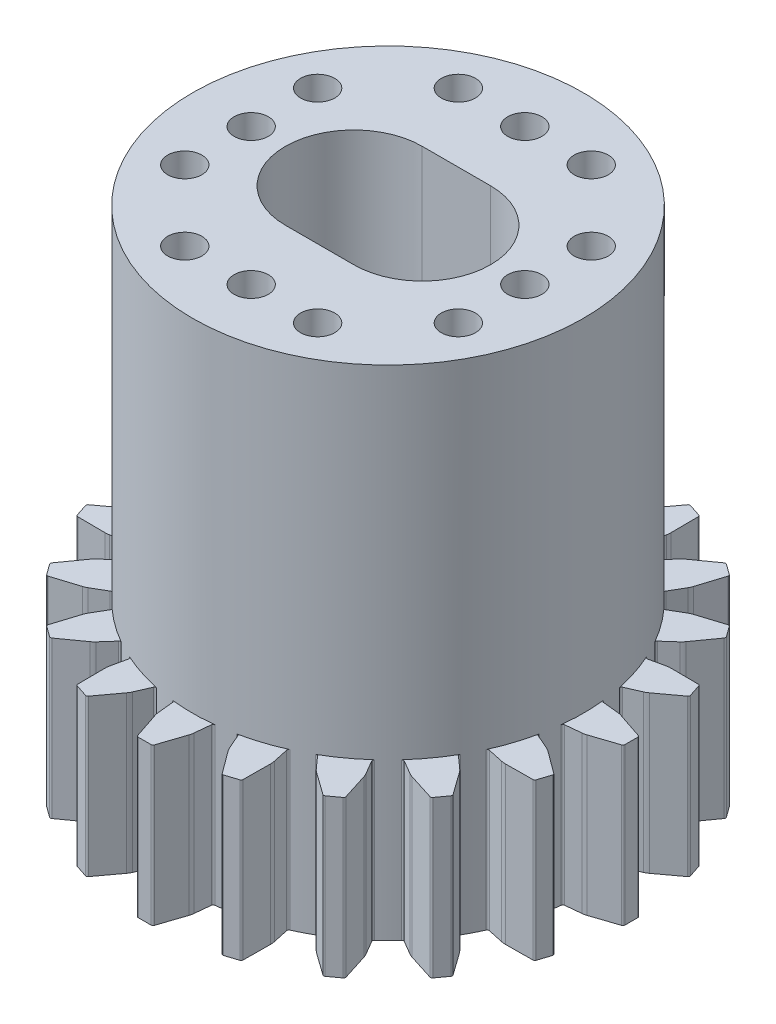
SolidWorks part; units mm, degrees
ref_plane "Front Plane" through (0, 0, 0) normal (0, 0, 1) x (1, 0, 0)
ref_plane "Top Plane" through (0, 0, 0) normal (0, 1, 0) x (1, 0, 0)
ref_plane "Right Plane" through (0, 0, 0) normal (1, 0, 0) x (0, 0, -1)
sketch "Sketch1" plane through (0, 0, 0) normal (0, 1, 0) x (1, 0, 0)
  line L0 (0, 23.8701) -> (0, -17.0658) construction
  line L1 (-0.9919, 10.0309) -> (-0.9111, 10.8389)
  line L2 (-0.8647, 11.0557) -> (-0.4228, 12.3815)
  line L3 (-0.3279, 12.4499) -> (0.3279, 12.4499)
  line L4 (0.4228, 12.3815) -> (0.8647, 11.0557)
  line L5 (0.9111, 10.8389) -> (0.9919, 10.0309)
  line L6 (2.1564, 9.8465) -> (2.4829, 10.59)
  line L7 (2.594, 10.7818) -> (3.424, 11.9062)
  line L8 (3.5353, 11.9419) -> (4.1591, 11.7392)
  line L9 (4.2282, 11.6449) -> (4.2388, 10.2473)
  line L10 (4.2159, 10.0269) -> (4.0431, 9.2334)
  line L11 (5.0936, 8.6982) -> (5.6339, 9.3044)
  line L12 (5.7988, 9.4525) -> (6.9356, 10.2654)
  line L13 (7.0526, 10.2649) -> (7.5831, 9.8794)
  line L14 (7.6197, 9.7683) -> (7.1979, 8.4359)
  line L15 (7.1081, 8.2333) -> (6.6985, 7.5322)
  line L16 (7.5322, 6.6985) -> (8.2333, 7.1081)
  line L17 (8.4359, 7.1979) -> (9.7683, 7.6197)
  line L18 (9.8794, 7.5831) -> (10.2649, 7.0526)
  line L19 (10.2654, 6.9356) -> (9.4525, 5.7988)
  line L20 (9.3044, 5.6339) -> (8.6982, 5.0936)
  line L21 (9.2334, 4.0431) -> (10.0269, 4.2159)
  line L22 (10.2473, 4.2388) -> (11.6449, 4.2282)
  line L23 (11.7392, 4.1591) -> (11.9419, 3.5353)
  line L24 (11.9062, 3.424) -> (10.7818, 2.594)
  line L25 (10.59, 2.4829) -> (9.8465, 2.1564)
  line L26 (10.0309, 0.9919) -> (10.8389, 0.9111)
  line L27 (11.0557, 0.8647) -> (12.3815, 0.4228)
  line L28 (12.4499, 0.3279) -> (12.4499, -0.3279)
  line L29 (12.3815, -0.4228) -> (11.0557, -0.8647)
  line L30 (10.8389, -0.9111) -> (10.0309, -0.9919)
  line L31 (9.8465, -2.1564) -> (10.59, -2.4829)
  line L32 (10.7818, -2.594) -> (11.9062, -3.424)
  line L33 (11.9419, -3.5353) -> (11.7392, -4.1591)
  line L34 (11.6449, -4.2282) -> (10.2473, -4.2388)
  line L35 (10.0269, -4.2159) -> (9.2334, -4.0431)
  line L36 (8.6982, -5.0936) -> (9.3044, -5.6339)
  line L37 (9.4525, -5.7988) -> (10.2654, -6.9356)
  line L38 (10.2649, -7.0526) -> (9.8794, -7.5831)
  line L39 (9.7683, -7.6197) -> (8.4359, -7.1979)
  line L40 (8.2333, -7.1081) -> (7.5322, -6.6985)
  line L41 (6.6985, -7.5322) -> (7.1081, -8.2333)
  line L42 (7.1979, -8.4359) -> (7.6197, -9.7683)
  line L43 (7.5831, -9.8794) -> (7.0526, -10.2649)
  line L44 (6.9356, -10.2654) -> (5.7988, -9.4525)
  line L45 (5.6339, -9.3044) -> (5.0936, -8.6982)
  line L46 (4.0431, -9.2334) -> (4.2159, -10.0269)
  line L47 (4.2388, -10.2473) -> (4.2282, -11.6449)
  line L48 (4.1591, -11.7392) -> (3.5353, -11.9419)
  line L49 (3.424, -11.9062) -> (2.594, -10.7818)
  line L50 (2.4829, -10.59) -> (2.1564, -9.8465)
  line L51 (0.9919, -10.0309) -> (0.9111, -10.8389)
  line L52 (0.8647, -11.0557) -> (0.4228, -12.3815)
  line L53 (0.3279, -12.4499) -> (-0.3279, -12.4499)
  line L54 (-0.4228, -12.3815) -> (-0.8647, -11.0557)
  line L55 (-0.9111, -10.8389) -> (-0.9919, -10.0309)
  line L56 (-2.1564, -9.8465) -> (-2.4829, -10.59)
  line L57 (-2.594, -10.7818) -> (-3.424, -11.9062)
  line L58 (-3.5353, -11.9419) -> (-4.1591, -11.7392)
  line L59 (-4.2282, -11.6449) -> (-4.2388, -10.2473)
  line L60 (-4.2159, -10.0269) -> (-4.0431, -9.2334)
  line L61 (-5.0936, -8.6982) -> (-5.6339, -9.3044)
  line L62 (-5.7988, -9.4525) -> (-6.9356, -10.2654)
  line L63 (-7.0526, -10.2649) -> (-7.5831, -9.8794)
  line L64 (-7.6197, -9.7683) -> (-7.1979, -8.4359)
  line L65 (-7.1081, -8.2333) -> (-6.6985, -7.5322)
  line L66 (-7.5322, -6.6985) -> (-8.2333, -7.1081)
  line L67 (-8.4359, -7.1979) -> (-9.7683, -7.6197)
  line L68 (-9.8794, -7.5831) -> (-10.2649, -7.0526)
  line L69 (-10.2654, -6.9356) -> (-9.4525, -5.7988)
  line L70 (-9.3044, -5.6339) -> (-8.6982, -5.0936)
  line L71 (-9.2334, -4.0431) -> (-10.0269, -4.2159)
  line L72 (-10.2473, -4.2388) -> (-11.6449, -4.2282)
  line L73 (-11.7392, -4.1591) -> (-11.9419, -3.5353)
  line L74 (-11.9062, -3.424) -> (-10.7818, -2.594)
  line L75 (-10.59, -2.4829) -> (-9.8465, -2.1564)
  line L76 (-10.0309, -0.9919) -> (-10.8389, -0.9111)
  line L77 (-11.0557, -0.8647) -> (-12.3815, -0.4228)
  line L78 (-12.4499, -0.3279) -> (-12.4499, 0.3279)
  line L79 (-12.3815, 0.4228) -> (-11.0557, 0.8647)
  line L80 (-10.8389, 0.9111) -> (-10.0309, 0.9919)
  line L81 (-9.8465, 2.1564) -> (-10.59, 2.4829)
  line L82 (-10.7818, 2.594) -> (-11.9062, 3.424)
  line L83 (-11.9419, 3.5353) -> (-11.7392, 4.1591)
  line L84 (-11.6449, 4.2282) -> (-10.2473, 4.2388)
  line L85 (-10.0269, 4.2159) -> (-9.2334, 4.0431)
  line L86 (-8.6982, 5.0936) -> (-9.3044, 5.6339)
  line L87 (-9.4525, 5.7988) -> (-10.2654, 6.9356)
  line L88 (-10.2649, 7.0526) -> (-9.8794, 7.5831)
  line L89 (-9.7683, 7.6197) -> (-8.4359, 7.1979)
  line L90 (-8.2333, 7.1081) -> (-7.5322, 6.6985)
  line L91 (-6.6985, 7.5322) -> (-7.1081, 8.2333)
  line L92 (-7.1979, 8.4359) -> (-7.6197, 9.7683)
  line L93 (-7.5831, 9.8794) -> (-7.0526, 10.2649)
  line L94 (-6.9356, 10.2654) -> (-5.7988, 9.4525)
  line L95 (-5.6339, 9.3044) -> (-5.0936, 8.6982)
  line L96 (-4.0431, 9.2334) -> (-4.2159, 10.0269)
  line L97 (-4.2388, 10.2473) -> (-4.2282, 11.6449)
  line L98 (-4.1591, 11.7392) -> (-3.5353, 11.9419)
  line L99 (-3.424, 11.9062) -> (-2.594, 10.7818)
  line L100 (-2.4829, 10.59) -> (-2.1564, 9.8465)
  arc A0 (-1.0806, 9.9414) -> (-2.0444, 9.7888) centre (0, 0) ccw
  arc A1 (0.8647, 11.0557) -> (0.9111, 10.8389) centre (-0.0839, 10.7394) cw
  arc A2 (-0.9111, 10.8389) -> (-0.8647, 11.0557) centre (0.0839, 10.7394) cw
  arc A3 (0.3279, 12.4499) -> (0.4228, 12.3815) centre (0.3279, 12.3499) cw
  arc A4 (-0.4228, 12.3815) -> (-0.3279, 12.4499) centre (-0.3279, 12.3499) cw
  arc A5 (0.9919, 10.0309) -> (1.0806, 9.9414) centre (1.0914, 10.0409) ccw
  arc A6 (-0.9919, 10.0309) -> (-1.0806, 9.9414) centre (-1.0914, 10.0409) cw
  arc A7 (2.1564, 9.8465) -> (2.0444, 9.7888) centre (2.0648, 9.8867) cw
  arc A8 (2.4829, 10.59) -> (2.594, 10.7818) centre (3.3985, 10.1879) cw
  arc A9 (3.424, 11.9062) -> (3.5353, 11.9419) centre (3.5044, 11.8468) cw
  arc A10 (4.1591, 11.7392) -> (4.2282, 11.6449) centre (4.1282, 11.6441) cw
  arc A11 (4.2388, 10.2473) -> (4.2159, 10.0269) centre (3.2388, 10.2397) cw
  arc A12 (4.0431, 9.2334) -> (4.0998, 9.121) centre (4.1408, 9.2122) ccw
  arc A13 (5.0936, 8.6982) -> (4.9692, 8.678) centre (5.0189, 8.7647) cw
  arc A14 (5.6339, 9.3044) -> (5.7988, 9.4525) centre (6.3804, 8.639) cw
  arc A15 (6.9356, 10.2654) -> (7.0526, 10.2649) centre (6.9938, 10.184) cw
  arc A16 (7.5831, 9.8794) -> (7.6197, 9.7683) centre (7.5244, 9.7985) cw
  arc A17 (7.1979, 8.4359) -> (7.1081, 8.2333) centre (6.2446, 8.7377) cw
  arc A18 (6.6985, 7.5322) -> (6.7177, 7.4076) centre (6.7848, 7.4817) ccw
  arc A19 (7.5322, 6.6985) -> (7.4076, 6.7177) centre (7.4817, 6.7848) cw
  arc A20 (8.2333, 7.1081) -> (8.4359, 7.1979) centre (8.7377, 6.2446) cw
  arc A21 (9.7683, 7.6197) -> (9.8794, 7.5831) centre (9.7985, 7.5244) cw
  arc A22 (10.2649, 7.0526) -> (10.2654, 6.9356) centre (10.184, 6.9938) cw
  arc A23 (9.4525, 5.7988) -> (9.3044, 5.6339) centre (8.639, 6.3804) cw
  arc A24 (8.6982, 5.0936) -> (8.678, 4.9692) centre (8.7647, 5.0189) ccw
  arc A25 (9.2334, 4.0431) -> (9.121, 4.0998) centre (9.2122, 4.1408) cw
  arc A26 (10.0269, 4.2159) -> (10.2473, 4.2388) centre (10.2397, 3.2388) cw
  arc A27 (11.6449, 4.2282) -> (11.7392, 4.1591) centre (11.6441, 4.1282) cw
  arc A28 (11.9419, 3.5353) -> (11.9062, 3.424) centre (11.8468, 3.5044) cw
  arc A29 (10.7818, 2.594) -> (10.59, 2.4829) centre (10.1879, 3.3985) cw
  arc A30 (9.8465, 2.1564) -> (9.7888, 2.0444) centre (9.8867, 2.0648) ccw
  arc A31 (10.0309, 0.9919) -> (9.9414, 1.0806) centre (10.0409, 1.0914) cw
  arc A32 (10.8389, 0.9111) -> (11.0557, 0.8647) centre (10.7394, -0.0839) cw
  arc A33 (12.3815, 0.4228) -> (12.4499, 0.3279) centre (12.3499, 0.3279) cw
  arc A34 (12.4499, -0.3279) -> (12.3815, -0.4228) centre (12.3499, -0.3279) cw
  arc A35 (11.0557, -0.8647) -> (10.8389, -0.9111) centre (10.7394, 0.0839) cw
  arc A36 (10.0309, -0.9919) -> (9.9414, -1.0806) centre (10.0409, -1.0914) ccw
  arc A37 (9.8465, -2.1564) -> (9.7888, -2.0444) centre (9.8867, -2.0648) cw
  arc A38 (10.59, -2.4829) -> (10.7818, -2.594) centre (10.1879, -3.3985) cw
  arc A39 (11.9062, -3.424) -> (11.9419, -3.5353) centre (11.8468, -3.5044) cw
  arc A40 (11.7392, -4.1591) -> (11.6449, -4.2282) centre (11.6441, -4.1282) cw
  arc A41 (10.2473, -4.2388) -> (10.0269, -4.2159) centre (10.2397, -3.2388) cw
  arc A42 (9.2334, -4.0431) -> (9.121, -4.0998) centre (9.2122, -4.1408) ccw
  arc A43 (8.6982, -5.0936) -> (8.678, -4.9692) centre (8.7647, -5.0189) cw
  arc A44 (9.3044, -5.6339) -> (9.4525, -5.7988) centre (8.639, -6.3804) cw
  arc A45 (10.2654, -6.9356) -> (10.2649, -7.0526) centre (10.184, -6.9938) cw
  arc A46 (9.8794, -7.5831) -> (9.7683, -7.6197) centre (9.7985, -7.5244) cw
  arc A47 (8.4359, -7.1979) -> (8.2333, -7.1081) centre (8.7377, -6.2446) cw
  arc A48 (7.5322, -6.6985) -> (7.4076, -6.7177) centre (7.4817, -6.7848) ccw
  arc A49 (6.6985, -7.5322) -> (6.7177, -7.4076) centre (6.7848, -7.4817) cw
  arc A50 (7.1081, -8.2333) -> (7.1979, -8.4359) centre (6.2446, -8.7377) cw
  arc A51 (7.6197, -9.7683) -> (7.5831, -9.8794) centre (7.5244, -9.7985) cw
  arc A52 (7.0526, -10.2649) -> (6.9356, -10.2654) centre (6.9938, -10.184) cw
  arc A53 (5.7988, -9.4525) -> (5.6339, -9.3044) centre (6.3804, -8.639) cw
  arc A54 (5.0936, -8.6982) -> (4.9692, -8.678) centre (5.0189, -8.7647) ccw
  arc A55 (4.0431, -9.2334) -> (4.0998, -9.121) centre (4.1408, -9.2122) cw
  arc A56 (4.2159, -10.0269) -> (4.2388, -10.2473) centre (3.2388, -10.2397) cw
  arc A57 (4.2282, -11.6449) -> (4.1591, -11.7392) centre (4.1282, -11.6441) cw
  arc A58 (3.5353, -11.9419) -> (3.424, -11.9062) centre (3.5044, -11.8468) cw
  arc A59 (2.594, -10.7818) -> (2.4829, -10.59) centre (3.3985, -10.1879) cw
  arc A60 (2.1564, -9.8465) -> (2.0444, -9.7888) centre (2.0648, -9.8867) ccw
  arc A61 (0.9919, -10.0309) -> (1.0806, -9.9414) centre (1.0914, -10.0409) cw
  arc A62 (0.9111, -10.8389) -> (0.8647, -11.0557) centre (-0.0839, -10.7394) cw
  arc A63 (0.4228, -12.3815) -> (0.3279, -12.4499) centre (0.3279, -12.3499) cw
  arc A64 (-0.3279, -12.4499) -> (-0.4228, -12.3815) centre (-0.3279, -12.3499) cw
  arc A65 (-0.8647, -11.0557) -> (-0.9111, -10.8389) centre (0.0839, -10.7394) cw
  arc A66 (-0.9919, -10.0309) -> (-1.0806, -9.9414) centre (-1.0914, -10.0409) ccw
  arc A67 (-2.1564, -9.8465) -> (-2.0444, -9.7888) centre (-2.0648, -9.8867) cw
  arc A68 (-2.4829, -10.59) -> (-2.594, -10.7818) centre (-3.3985, -10.1879) cw
  arc A69 (-3.424, -11.9062) -> (-3.5353, -11.9419) centre (-3.5044, -11.8468) cw
  arc A70 (-4.1591, -11.7392) -> (-4.2282, -11.6449) centre (-4.1282, -11.6441) cw
  arc A71 (-4.2388, -10.2473) -> (-4.2159, -10.0269) centre (-3.2388, -10.2397) cw
  arc A72 (-4.0431, -9.2334) -> (-4.0998, -9.121) centre (-4.1408, -9.2122) ccw
  arc A73 (-5.0936, -8.6982) -> (-4.9692, -8.678) centre (-5.0189, -8.7647) cw
  arc A74 (-5.6339, -9.3044) -> (-5.7988, -9.4525) centre (-6.3804, -8.639) cw
  arc A75 (-6.9356, -10.2654) -> (-7.0526, -10.2649) centre (-6.9938, -10.184) cw
  arc A76 (-7.5831, -9.8794) -> (-7.6197, -9.7683) centre (-7.5244, -9.7985) cw
  arc A77 (-7.1979, -8.4359) -> (-7.1081, -8.2333) centre (-6.2446, -8.7377) cw
  arc A78 (-6.6985, -7.5322) -> (-6.7177, -7.4076) centre (-6.7848, -7.4817) ccw
  arc A79 (-7.5322, -6.6985) -> (-7.4076, -6.7177) centre (-7.4817, -6.7848) cw
  arc A80 (-8.2333, -7.1081) -> (-8.4359, -7.1979) centre (-8.7377, -6.2446) cw
  arc A81 (-9.7683, -7.6197) -> (-9.8794, -7.5831) centre (-9.7985, -7.5244) cw
  arc A82 (-10.2649, -7.0526) -> (-10.2654, -6.9356) centre (-10.184, -6.9938) cw
  arc A83 (-9.4525, -5.7988) -> (-9.3044, -5.6339) centre (-8.639, -6.3804) cw
  arc A84 (-8.6982, -5.0936) -> (-8.678, -4.9692) centre (-8.7647, -5.0189) ccw
  arc A85 (-9.2334, -4.0431) -> (-9.121, -4.0998) centre (-9.2122, -4.1408) cw
  arc A86 (-10.0269, -4.2159) -> (-10.2473, -4.2388) centre (-10.2397, -3.2388) cw
  arc A87 (-11.6449, -4.2282) -> (-11.7392, -4.1591) centre (-11.6441, -4.1282) cw
  arc A88 (-11.9419, -3.5353) -> (-11.9062, -3.424) centre (-11.8468, -3.5044) cw
  arc A89 (-10.7818, -2.594) -> (-10.59, -2.4829) centre (-10.1879, -3.3985) cw
  arc A90 (-9.8465, -2.1564) -> (-9.7888, -2.0444) centre (-9.8867, -2.0648) ccw
  arc A91 (-10.0309, -0.9919) -> (-9.9414, -1.0806) centre (-10.0409, -1.0914) cw
  arc A92 (-10.8389, -0.9111) -> (-11.0557, -0.8647) centre (-10.7394, 0.0839) cw
  arc A93 (-12.3815, -0.4228) -> (-12.4499, -0.3279) centre (-12.3499, -0.3279) cw
  arc A94 (-12.4499, 0.3279) -> (-12.3815, 0.4228) centre (-12.3499, 0.3279) cw
  arc A95 (-11.0557, 0.8647) -> (-10.8389, 0.9111) centre (-10.7394, -0.0839) cw
  arc A96 (-10.0309, 0.9919) -> (-9.9414, 1.0806) centre (-10.0409, 1.0914) ccw
  arc A97 (-9.8465, 2.1564) -> (-9.7888, 2.0444) centre (-9.8867, 2.0648) cw
  arc A98 (-10.59, 2.4829) -> (-10.7818, 2.594) centre (-10.1879, 3.3985) cw
  arc A99 (-11.9062, 3.424) -> (-11.9419, 3.5353) centre (-11.8468, 3.5044) cw
  arc A100 (-11.7392, 4.1591) -> (-11.6449, 4.2282) centre (-11.6441, 4.1282) cw
  arc A101 (-10.2473, 4.2388) -> (-10.0269, 4.2159) centre (-10.2397, 3.2388) cw
  arc A102 (-9.2334, 4.0431) -> (-9.121, 4.0998) centre (-9.2122, 4.1408) ccw
  arc A103 (-8.6982, 5.0936) -> (-8.678, 4.9692) centre (-8.7647, 5.0189) cw
  arc A104 (-9.3044, 5.6339) -> (-9.4525, 5.7988) centre (-8.639, 6.3804) cw
  arc A105 (-10.2654, 6.9356) -> (-10.2649, 7.0526) centre (-10.184, 6.9938) cw
  arc A106 (-9.8794, 7.5831) -> (-9.7683, 7.6197) centre (-9.7985, 7.5244) cw
  arc A107 (-8.4359, 7.1979) -> (-8.2333, 7.1081) centre (-8.7377, 6.2446) cw
  arc A108 (-7.5322, 6.6985) -> (-7.4076, 6.7177) centre (-7.4817, 6.7848) ccw
  arc A109 (-6.6985, 7.5322) -> (-6.7177, 7.4076) centre (-6.7848, 7.4817) cw
  arc A110 (-7.1081, 8.2333) -> (-7.1979, 8.4359) centre (-6.2446, 8.7377) cw
  arc A111 (-7.6197, 9.7683) -> (-7.5831, 9.8794) centre (-7.5244, 9.7985) cw
  arc A112 (-7.0526, 10.2649) -> (-6.9356, 10.2654) centre (-6.9938, 10.184) cw
  arc A113 (-5.7988, 9.4525) -> (-5.6339, 9.3044) centre (-6.3804, 8.639) cw
  arc A114 (-5.0936, 8.6982) -> (-4.9692, 8.678) centre (-5.0189, 8.7647) ccw
  arc A115 (-4.0431, 9.2334) -> (-4.0998, 9.121) centre (-4.1408, 9.2122) cw
  arc A116 (-4.2159, 10.0269) -> (-4.2388, 10.2473) centre (-3.2388, 10.2397) cw
  arc A117 (-4.2282, 11.6449) -> (-4.1591, 11.7392) centre (-4.1282, 11.6441) cw
  arc A118 (-3.5353, 11.9419) -> (-3.424, 11.9062) centre (-3.5044, 11.8468) cw
  arc A119 (-2.594, 10.7818) -> (-2.4829, 10.59) centre (-3.3985, 10.1879) cw
  arc A120 (-2.1564, 9.8465) -> (-2.0444, 9.7888) centre (-2.0648, 9.8867) ccw
  arc A121 (-4.0998, 9.121) -> (-4.9692, 8.678) centre (0, 0) ccw
  arc A122 (-6.7177, 7.4076) -> (-7.4076, 6.7177) centre (0, 0) ccw
  arc A123 (-8.678, 4.9692) -> (-9.121, 4.0998) centre (0, 0) ccw
  arc A124 (-9.7888, 2.0444) -> (-9.9414, 1.0806) centre (0, 0) ccw
  arc A125 (-9.121, -4.0998) -> (-8.678, -4.9692) centre (0, 0) ccw
  arc A126 (-7.4076, -6.7177) -> (-6.7177, -7.4076) centre (0, 0) ccw
  arc A127 (-4.9692, -8.678) -> (-4.0998, -9.121) centre (0, 0) ccw
  arc A128 (-2.0444, -9.7888) -> (-1.0806, -9.9414) centre (0, 0) ccw
  arc A129 (1.0806, -9.9414) -> (2.0444, -9.7888) centre (0, 0) ccw
  arc A130 (4.0998, -9.121) -> (4.9692, -8.678) centre (0, 0) ccw
  arc A131 (6.7177, -7.4076) -> (7.4076, -6.7177) centre (0, 0) ccw
  arc A132 (8.678, -4.9692) -> (9.121, -4.0998) centre (0, 0) ccw
  arc A133 (9.7888, -2.0444) -> (9.9414, -1.0806) centre (0, 0) ccw
  arc A134 (9.9414, 1.0806) -> (9.7888, 2.0444) centre (0, 0) ccw
  arc A135 (9.121, 4.0998) -> (8.678, 4.9692) centre (0, 0) ccw
  arc A136 (7.4076, 6.7177) -> (6.7177, 7.4076) centre (0, 0) ccw
  arc A137 (4.9692, 8.678) -> (4.0998, 9.121) centre (0, 0) ccw
  arc A138 (2.0444, 9.7888) -> (1.0806, 9.9414) centre (0, 0) ccw
  arc A139 (-9.9414, -1.0806) -> (-9.7888, -2.0444) centre (0, 0) ccw
  point P7 (0, 12.4499)
  point P12 (0, 10)
  point P21 (0.9, 10.9499)
  point P24 (-0.9, 10.9499)
  point P27 (0.4, 12.4499)
  point P30 (-0.4, 12.4499)
  point P32 (1, 9.9499)
  point P35 (-1, 9.9499)
  point P374 (0, 0)
  dimension "D1" = 20
  dimension "D9" = 1
  dimension "D10" = 0.1
  dimension "D11" = 0.1
  dimension "D2" = 0.8
  dimension "D3" = 1
  dimension "D4" = 2.5
  dimension "D5" = 1
  dimension "D6" = 2
  dimension "D7" = 0.1
  dimension "D8" = 0.1
  dimension "D12" = 20
extrude "Boss-Extrude1" add sketch "Sketch1" along normal blind 8
sketch "Sketch2" plane through (0, 0, 0) normal (0, -1, 0) x (1, 0, 0)
  circle A0 centre (0, 0) radius 8
  circle A1 centre (0, 0) radius 5.5
  dimension "D1" = 16
  dimension "D2" = 11
extrude "Cut-Extrude1" cut sketch "Sketch2" against normal blind 2.9
sketch "Sketch3" plane through (0, 8, 0) normal (0, 1, 0) x (1, 0, 0)
  circle A0 centre (0, 0) radius 10
  dimension "D1" = 20
extrude "Boss-Extrude2" add sketch "Sketch3" along normal blind 17.5
sketch "Sketch4" plane through (0, 25.5, 0) normal (0, 1, 0) x (1, 0, 0)
  circle A0 centre (0, 7) radius 0.875
  circle A1 centre (3.4, 7) radius 0.875
  circle A2 centre (-3.4, 7) radius 0.875
  circle A3 centre (7, 3.4) radius 0.875
  circle A4 centre (7, 0) radius 0.875
  circle A5 centre (7, -3.4) radius 0.875
  circle A6 centre (3.4, -7) radius 0.875
  circle A7 centre (0, -7) radius 0.875
  circle A8 centre (-3.4, -7) radius 0.875
  circle A9 centre (-7, -3.4) radius 0.875
  circle A10 centre (-7, 0) radius 0.875
  circle A11 centre (-7, 3.4) radius 0.875
  point P27 (0, 0)
  dimension "D5" = 1.75
  dimension "D1" = 7
  dimension "D2" = 7
  dimension "D3" = 4
  dimension "D6" = 3.4
  dimension "D7" = 3.4
extrude "Cut-Extrude2" cut sketch "Sketch4" against normal blind 15
sketch "Sketch5" plane through (0, 0, 0) normal (0, -1, 0) x (1, 0, 0)
  line L0 (-1.75, 3.5) -> (1.75, 3.5)
  line L1 (-1.75, -3.5) -> (1.75, -3.5)
  line L2 (-1.75, 0) -> (1.75, 0) construction
  arc A0 (-1.75, 3.5) -> (-1.75, -3.5) centre (-1.75, 0) ccw
  arc A1 (1.75, -3.5) -> (1.75, 3.5) centre (1.75, 0) ccw
  point P6 (0, 0)
  dimension "D2" = 3.5
  dimension "D1" = 3.5
extrude "Cut-Extrude5" cut sketch "Sketch5" along direction (0, 1, 0) on the side against the normal blind 30 and the other way through all
sketch "Sketch6" plane through (0, 25.5, 0) normal (0, 1, 0) x (1, 0, 0)
  line L0 (-18.0612, 0) -> (18.3147, 0) construction
  line L1 (0, 13.2248) -> (0, -13.8666) construction
  circle A0 centre (0.1267, 0) radius 2.1107
  point P5 (0, 0)
ref_point "Point1"
